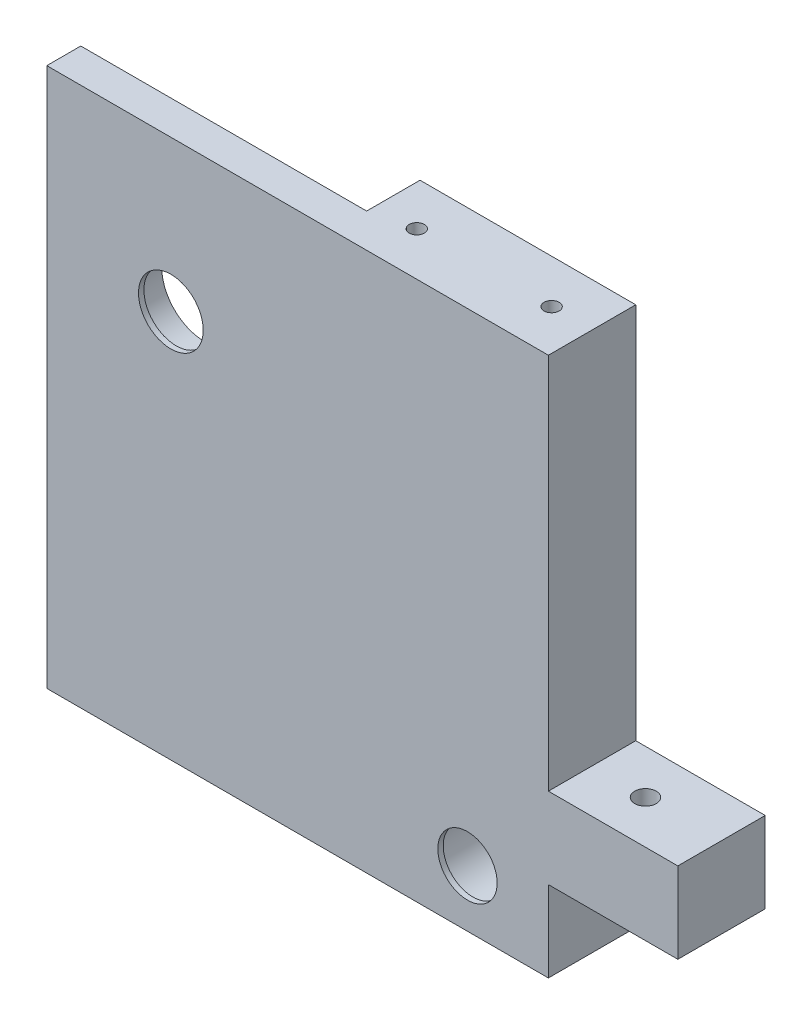
SolidWorks part; units mm, degrees
ref_plane "Front Plane" through (0, 0, 0) normal (0, 0, 1) x (1, 0, 0)
ref_plane "Top Plane" through (0, 0, 0) normal (0, 1, 0) x (1, 0, 0)
ref_plane "Right Plane" through (0, 0, 0) normal (1, 0, 0) x (0, 0, -1)
sketch "Sketch1" plane through (0, 0, 0) normal (0, 0, 1) x (1, 0, 0)
  line L1 (-76.1871, 64.9281) -> (16.8129, 64.9281)
  line L2 (-76.1871, 64.9281) -> (-76.1871, -35.0719)
  line L3 (-76.1871, -35.0719) -> (16.8129, -35.0719)
  line L4 (16.8129, 64.9281) -> (16.8129, -35.0719)
  dimension "D1" = 93
  dimension "D2" = 100
extrude "Boss-Extrude2" add sketch "Sketch1" along normal blind 6.3 contours L1 L4 L3 L2
sketch "Sketch3" plane through (0, 0, 0) normal (0, 0, -1) x (-1, 0, 0)
  line L0 (76.1871, -35.0719) -> (-16.8129, -35.0719) construction
  line L1 (-16.8129, 64.9281) -> (23.1871, 64.9281)
  line L2 (-16.8129, 64.9281) -> (-16.8129, -35.0719)
  line L3 (-16.8129, -35.0719) -> (23.1871, -35.0719)
  line L4 (23.1871, 64.9281) -> (23.1871, -35.0719)
  line L5 (-16.8129, 64.9281) -> (-16.8129, -35.0719) construction
  dimension "D1" = 0
  dimension "D2" = 0
  dimension "D3" = 40
  dimension "D4" = 100
extrude "Boss-Extrude3" add sketch "Sketch3" along normal blind 9.9
sketch "Sketch4" plane through (16.8129, 0, 0) normal (1, 0, 0) x (0, 0, -1)
  line L0 (-6.3, 64.9281) -> (-6.3, -35.0719) construction
  line L1 (-6.3, -5.0719) -> (9.9, -5.0719)
  line L2 (-6.3, -5.0719) -> (-6.3, -20.0719)
  line L3 (-6.3, -20.0719) -> (9.9, -20.0719)
  line L4 (9.9, -5.0719) -> (9.9, -20.0719)
  line L5 (9.9, 64.9281) -> (9.9, -35.0719) construction
  line L6 (-6.3, -35.0719) -> (9.9, -35.0719) construction
  dimension "D1" = 15
  dimension "D2" = 15
extrude "Boss-Extrude4" add sketch "Sketch4" along normal blind 24
sketch "Sketch5" plane through (0, -5.0719, 0) normal (0, 1, 0) x (1, 0, 0)
  line L0 (40.8129, -6.3) -> (16.8129, -6.3) construction
  line L2 (16.8129, 9.9) -> (16.8129, -6.3) construction
  circle A0 centre (26.8129, 1.7) radius 2
  dimension "D2" = 4
  dimension "D3" = 10
  dimension "D1" = 8
extrude "Cut-Extrude1" cut sketch "Sketch5" against normal blind 50
sketch "Sketch6" plane through (0, 0, -9.9) normal (0, 0, -1) x (-1, 0, 0)
  line L0 (-16.8129, -35.0719) -> (23.1871, -35.0719) construction
  line L1 (-16.8129, -20.0719) -> (-16.8129, -35.0719) construction
  circle A0 centre (-1.8129, -24.5719) radius 7.5
  dimension "D1" = 15
  dimension "D2" = 10.5
  dimension "D3" = 15
extrude "Cut-Extrude2" cut sketch "Sketch6" against normal blind 50
sketch "Sketch7" plane through (0, 0, 0) normal (0, 0, -1) x (-1, 0, 0)
  line L0 (76.1871, -35.0719) -> (23.1871, -35.0719) construction
  line L2 (-16.8129, 64.9281) -> (-16.8129, -5.0719) construction
  circle A0 centre (53.1871, 36.9281) radius 8
  dimension "D1" = 16
  dimension "D2" = 72
  dimension "D3" = 70
extrude "Cut-Extrude3" cut sketch "Sketch7" against normal blind 50
extrude "Extrude-Thin1" add sketch "Sketch7<2>" along normal blind 1 from surface thin starting at face at (-45.1871, 36.9281, 6.3) thin type one direction reverse wall 2
sketch "Sketch7<2>" plane through (0, 0, 0) normal (0, 0, -1) x (-1, 0, 0) same geometry as "Sketch7"
extrude "Extrude-Thin2" add sketch "Sketch6<2>" along normal blind 1 from surface thin starting at face at (9.3129, -24.5719, 6.3) thin type one direction reverse wall 2
sketch "Sketch6<2>" plane through (0, 0, -9.9) normal (0, 0, -1) x (-1, 0, 0) same geometry as "Sketch6"
sketch "Sketch8" plane through (0, 64.9281, 0) normal (0, 1, 0) x (1, 0, 0)
  line L0 (-76.1871, -6.3) -> (16.8129, -6.3) construction
  line L1 (16.8129, 9.9) -> (-23.1871, 9.9)
  line L2 (16.8129, 9.9) -> (16.8129, -6.3)
  line L3 (16.8129, -6.3) -> (-23.1871, -6.3)
  line L4 (-23.1871, 9.9) -> (-23.1871, -6.3)
  line L5 (16.8129, 9.9) -> (-23.1871, -6.3) construction
  line L6 (16.8129, -6.3) -> (-23.1871, 9.9) construction
  line L7 (-23.1871, 9.9) -> (-23.1871, 0) construction
  circle A0 centre (9.3129, 1.8) radius 1.4
  circle A1 centre (-15.6871, 1.8) radius 1.4
  point P4 (-3.1871, 1.8)
  dimension "D1" = 25
  dimension "D2" = 7.5
  dimension "D3" = 2.8
  dimension "D4" = 2.8
  dimension "D5" = 8.1
  dimension "D6" = 8.1
extrude "Cut-Extrude4" cut sketch "Sketch8" against normal blind 20 contours A1 | A0 region at (-15.6871, 64.9281, -1.8)
